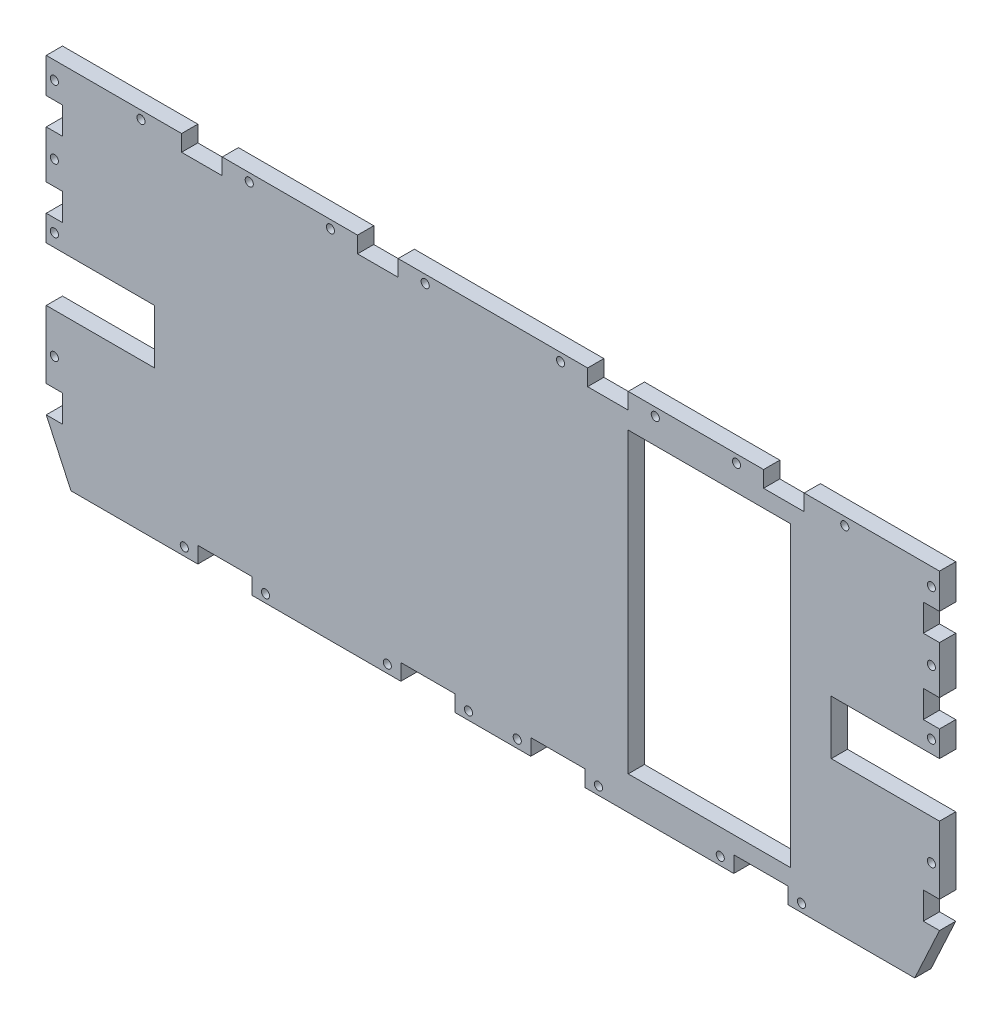
SolidWorks part; units mm, degrees
ref_plane "Plan de face" through (0, 0, 0) normal (0, 0, 1) x (1, 0, 0)
ref_plane "Plan de dessus" through (0, 0, 0) normal (0, 1, 0) x (1, 0, 0)
ref_plane "Plan de droite" through (0, 0, 0) normal (1, 0, 0) x (0, 0, -1)
sketch "Esquisse1" plane through (0, 0, 0) normal (0, 0, 1) x (1, 0, 0)
  line L0 (0, 124.9429) -> (0, -204.46) construction
  line L1 (-165, 96.73) -> (165, 96.73)
  line L2 (165, 96.73) -> (165, -18.27)
  line L3 (165, -18.27) -> (123, -109.0224)
  line L4 (123, -109.0224) -> (-123, -109.0224)
  line L5 (-211.9802, 0) -> (248.5953, 0) construction
  line L6 (-123, -109.0224) -> (-165, -18.27)
  line L7 (-165, -18.27) -> (-165, 96.73)
  dimension "D2" = 165
  dimension "D3" = 330
  dimension "D4" = 100
  dimension "D5" = 115
  dimension "D6" = 100
  dimension "D7" = 246
  dimension "D8" = 205.7524
  dimension "D9" = 96.73
  dimension "D10" = 115
extrude "Boss.-Extru.1" add sketch "Esquisse1" along normal blind 6
sketch "Esquisse3" plane through (0, 0, 0) normal (0, 0, -1) x (-1, 0, 0)
  line L0 (165, 96.73) -> (165, -18.27) construction
  line L1 (165, -18.27) -> (159, -18.27)
  line L2 (165, -18.27) -> (165, -8.27)
  line L3 (165, -8.27) -> (159, -8.27)
  line L4 (159, -18.27) -> (159, -8.27)
  line L5 (123, -109.0224) -> (-123, -109.0224) construction
  line L6 (165, 73.8526) -> (159, 73.8526)
  line L7 (165, 73.8526) -> (165, 83.8526)
  line L8 (165, 83.8526) -> (159, 83.8526)
  line L9 (159, 73.8526) -> (159, 83.8526)
  line L10 (-14, -38.02) -> (-14, -32.02)
  line L11 (109, -38.02) -> (89, -38.02)
  line L12 (109, -38.02) -> (109, -32.02)
  line L13 (109, -32.02) -> (89, -32.02)
  line L14 (-159, 46.23) -> (-159, 56.23)
  line L15 (0, -209.4812) -> (0, 177.1799) construction
  line L16 (-110, 84.355) -> (-50, 84.355)
  line L17 (-165, 56.23) -> (-159, 56.23)
  line L18 (89, -38.02) -> (89, -32.02)
  line L19 (34, -38.02) -> (14, -38.02)
  line L20 (34, -38.02) -> (34, -32.02)
  line L21 (34, -32.02) -> (14, -32.02)
  line L22 (-159, 73.8526) -> (-159, 83.8526)
  line L23 (-165, 83.8526) -> (-159, 83.8526)
  line L24 (-165, 73.8526) -> (-165, 83.8526)
  line L25 (-165, 73.8526) -> (-159, 73.8526)
  line L26 (-159, -18.27) -> (-159, -8.27)
  line L27 (-165, -8.27) -> (-159, -8.27)
  line L28 (-165, -18.27) -> (-165, -8.27)
  line L29 (-165, -18.27) -> (-159, -18.27)
  line L30 (-165, 96.73) -> (165, 96.73) construction
  line L31 (115, 96.73) -> (100, 96.73)
  line L32 (115, 96.73) -> (115, 90.73)
  line L33 (115, 90.73) -> (100, 90.73)
  line L34 (100, 96.73) -> (100, 90.73)
  line L35 (-35, 96.73) -> (-35, 90.73)
  line L36 (50, 96.73) -> (35, 96.73)
  line L37 (50, 96.73) -> (50, 90.73)
  line L38 (50, 90.73) -> (35, 90.73)
  line L39 (35, 96.73) -> (35, 90.73)
  line L40 (-50, 90.73) -> (-35, 90.73)
  line L41 (-50, 96.73) -> (-50, 90.73)
  line L42 (-50, 96.73) -> (-35, 96.73)
  line L43 (-100, 96.73) -> (-100, 90.73)
  line L44 (-115, 90.73) -> (-100, 90.73)
  line L45 (-115, 96.73) -> (-115, 90.73)
  line L46 (-115, 96.73) -> (-100, 96.73)
  line L47 (-165, 46.23) -> (-165, 56.23)
  line L48 (14, -38.02) -> (14, -32.02)
  line L49 (-34, -32.02) -> (-14, -32.02)
  line L50 (-34, -38.02) -> (-34, -32.02)
  line L51 (-34, -38.02) -> (-14, -38.02)
  line L52 (165, 46.23) -> (159, 46.23)
  line L53 (165, 46.23) -> (165, 56.23)
  line L54 (165, 56.23) -> (159, 56.23)
  line L55 (159, 46.23) -> (159, 56.23)
  line L56 (-165, 46.23) -> (-159, 46.23)
  line L57 (-89, -38.02) -> (-89, -32.02)
  line L58 (-109, -32.02) -> (-89, -32.02)
  line L59 (-109, -38.02) -> (-109, -32.02)
  line L60 (-109, -38.02) -> (-89, -38.02)
  line L61 (-165, -18.27) -> (-165, 96.73) construction
  line L62 (-110, 84.355) -> (-110, -25.645)
  line L63 (-110, -25.645) -> (-50, -25.645)
  line L64 (-50, 84.355) -> (-50, -25.645)
  line L66 (-165, 36.73) -> (-125, 36.73)
  line L67 (-165, 36.73) -> (-165, 16.73)
  line L68 (-165, 16.73) -> (-125, 16.73)
  line L69 (-125, 36.73) -> (-125, 16.73)
  line L70 (125, 36.73) -> (125, 16.73)
  line L71 (165, 16.73) -> (125, 16.73)
  line L72 (165, 36.73) -> (165, 16.73)
  line L73 (165, 36.73) -> (125, 36.73)
  dimension "D1" = 10
  dimension "D2" = 6
  dimension "D3" = 6
  dimension "D4" = 10
  dimension "D5" = 6
  dimension "D6" = 20
  dimension "D7" = 60
  dimension "D8" = 55
  dimension "D9" = 12.8774
  dimension "D10" = 15
  dimension "D11" = 15
  dimension "D12" = 50
  dimension "D13" = 50
  dimension "D14" = 6
  dimension "D15" = 110
  dimension "D16" = 56
  dimension "D17" = 15
  dimension "D18" = 6
  dimension "D19" = 10
  dimension "D20" = 40.5
  dimension "D21" = 6
  dimension "D22" = 6
  dimension "D23" = 20
  dimension "D24" = 71.0024
  dimension "D25" = 71.0024
  dimension "D26" = 60
  dimension "D27" = 20
  dimension "D28" = 40
  dimension "D29" = 6.375
extrude "Enlèv. mat.-Extru.2" cut sketch "Esquisse3" against normal blind 6
sketch "Esquisse4" plane through (0, 0, 0) normal (0, 0, -1) x (-1, 0, 0)
  line L0 (159, 73.8526) -> (165, 73.8526) construction
  line L1 (115, 90.73) -> (115, 96.73) construction
  line L2 (120.102, -35.02) -> (4.7601, -35.02) construction
  line L3 (14, -32.02) -> (14, -38.02) construction
  line L4 (34, -38.02) -> (34, -32.02) construction
  line L5 (89, -32.02) -> (89, -38.02) construction
  line L6 (115, 96.73) -> (165, 96.73) construction
  line L7 (109, -38.02) -> (109, -32.02) construction
  line L8 (165, 73.8526) -> (165, 56.23) construction
  line L9 (-120.102, -35.02) -> (-4.7601, -35.02) construction
  line L10 (165, 96.73) -> (165, 83.8526) construction
  line L11 (143.8632, 93.73) -> (0, 93.73) construction
  line L12 (50, 96.73) -> (100, 96.73) construction
  line L14 (100, 96.73) -> (100, 90.73) construction
  line L15 (50, 90.73) -> (50, 96.73) construction
  line L16 (35, 96.73) -> (35, 90.73) construction
  line L17 (0, 142.2997) -> (0, -202.2086) construction
  line L18 (-162, -8.8123) -> (-162, 103.5881) construction
  line L19 (-80, 84.355) -> (-80, -25.645) construction
  line L20 (159, 46.23) -> (165, 46.23) construction
  line L21 (165, -8.27) -> (159, -8.27) construction
  line L22 (162, -8.8123) -> (162, 103.5881) construction
  line L25 (-50, 84.355) -> (-110, 84.355) construction
  line L26 (-110, -25.645) -> (-50, -25.645) construction
  circle A0 centre (162, 1.92) radius 1.5
  circle A1 centre (114, -35.02) radius 1.5
  circle A2 centre (162, 65.0426) radius 1.5
  circle A3 centre (84, -35.02) radius 1.5
  circle A4 centre (39, -35.02) radius 1.5
  circle A5 centre (162, 90.29) radius 1.5
  circle A6 centre (9, -35.02) radius 1.5
  circle A7 centre (-9, -35.02) radius 1.5
  circle A8 centre (-39, -35.02) radius 1.5
  circle A9 centre (-84, -35.02) radius 1.5
  circle A10 centre (130, 93.73) radius 1.5
  circle A11 centre (-114, -35.02) radius 1.5
  circle A12 centre (90, 93.73) radius 1.5
  circle A13 centre (-162, 41.48) radius 1.5
  circle A14 centre (60, 93.73) radius 1.5
  circle A15 centre (25, 93.73) radius 1.5
  circle A18 centre (-25, 93.73) radius 1.5
  circle A19 centre (-60, 93.73) radius 1.5
  circle A20 centre (-90, 93.73) radius 1.5
  circle A21 centre (-130, 93.73) radius 1.5
  circle A22 centre (-162, 90.29) radius 1.5
  circle A23 centre (-162, 65.0426) radius 1.5
  circle A24 centre (-162, 1.92) radius 1.5
  circle A33 centre (162, 41.48) radius 1.5
  dimension "D1" = 3
  dimension "D3" = 3
  dimension "D10" = 3
  dimension "D11" = 3
  dimension "D12" = 3
  dimension "D13" = 5
  dimension "D14" = 5
  dimension "D18" = 3
  dimension "D19" = 3
  dimension "D29" = 3
  dimension "D31" = 3
  dimension "D33" = 3
  dimension "D34" = 3
  dimension "D35" = 4.75
  dimension "D40" = 10
  dimension "D5" = 10.19
  dimension "D8" = 15
  dimension "D15" = 5
  dimension "D16" = 5
  dimension "D23" = 3
  dimension "D9" = 3
  dimension "D6" = 8.81
  dimension "D7" = 6.44
  dimension "D24" = 3
  dimension "D26" = 3
  dimension "D28" = 3
  dimension "D38" = 10
  dimension "D41" = 25
  dimension "D42" = 10
extrude "Enlèv. mat.-Extru.3" cut sketch "Esquisse4" against normal blind 6
sketch "Esquisse5" plane through (0, 0, 0) normal (0, 0, -1) x (-1, 0, 0)
  line L0 (50, 96.73) -> (100, 96.73) construction
  line L1 (209.7155, -38.02) -> (-246.3297, -38.02)
  line L2 (209.7155, -38.02) -> (209.7155, -174.249)
  line L3 (209.7155, -174.249) -> (-246.3297, -174.249)
  line L4 (-246.3297, -38.02) -> (-246.3297, -174.249)
  dimension "D1" = 134.75
extrude "Enlèv. mat.-Extru.4" cut sketch "Esquisse5" against normal blind 6
